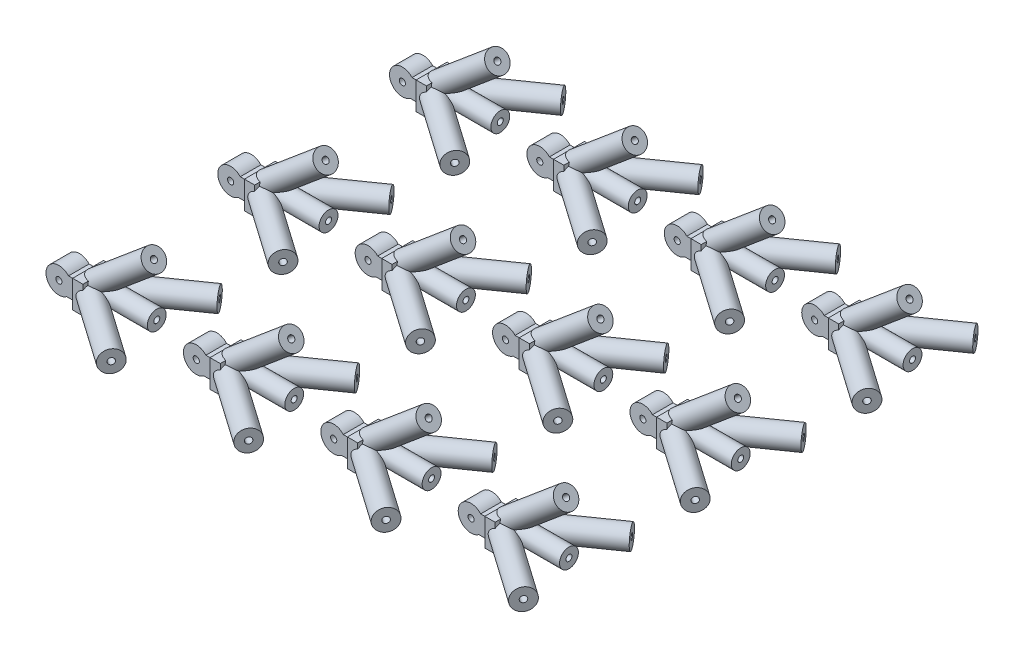
SolidWorks part; units mm, degrees
ref_plane "前视基准面" through (0, 0, 0) normal (0, 0, 1) x (1, 0, 0)
ref_plane "上视基准面" through (0, 0, 0) normal (0, 1, 0) x (1, 0, 0)
ref_plane "右视基准面" through (0, 0, 0) normal (1, 0, 0) x (0, 0, -1)
sketch "草图1" plane through (0, 0, 0) normal (0, 1, 0) x (1, 0, 0)
  line L0 (0, 0) -> (9.0107, 6.3093)
  line L1 (9.0107, 6.3093) -> (9.0107, -6.3093) construction
  line L2 (9.0107, -6.3093) -> (0, 0)
  line L3 (0, 0) -> (9.0107, 0) construction
  dimension "D1" = 11
  dimension "D2" = 35
sketch "草图2" plane through (0, 0, 0) normal (1, 0, 0) x (0, 0, -1)
  line L1 (-1.8, -1.6) -> (1.8, -1.6)
  line L2 (-1.8, -1.6) -> (-1.8, 1.6)
  line L3 (-1.8, 1.6) -> (1.8, 1.6)
  line L4 (1.8, -1.6) -> (1.8, 1.6)
  line L5 (-1.8, -1.6) -> (1.8, 1.6) construction
  line L6 (-1.8, 1.6) -> (1.8, -1.6) construction
  line L7 (-0.9562, -0.85) -> (0.9562, -0.85)
  line L8 (-0.9562, -0.85) -> (-0.9562, 0.85)
  line L9 (-0.9562, 0.85) -> (0.9562, 0.85)
  line L10 (0.9562, -0.85) -> (0.9562, 0.85)
  line L11 (-0.9562, -0.85) -> (0.9562, 0.85) construction
  line L12 (-0.9562, 0.85) -> (0.9562, -0.85) construction
  point P0 (0, 0)
  point P6 (0, 0)
  dimension "D1" = 3.2
  dimension "D2" = 1.7
  dimension "D3" = 3.6
extrude "凸台-拉伸1" add sketch "草图2" against normal blind 7
ref_plane "基准面1" through (9.0107, 0, 6.3093) normal (-0.8192, 0, -0.5736) x (-0.5736, 0, 0.8192)
sketch "草图3" plane through (9.0107, 0, 6.3093) normal (-0.8192, 0, -0.5736) x (-0.5736, 0, 0.8192)
  circle A0 centre (0, 0) radius 1.25
  circle A1 centre (0, 0) radius 0.36
  dimension "D1" = 2.5
  dimension "D2" = 0.72
extrude "凸台-拉伸2" add sketch "草图3" along normal up to surface (10.1247 mm away)
ref_plane "基准面2" through (9.0107, 0, -6.3093) normal (0.8192, 0, -0.5736) x (-0.5736, 0, -0.8192)
sketch "草图4" plane through (9.0107, 0, -6.3093) normal (0.8192, 0, -0.5736) x (-0.5736, 0, -0.8192)
  circle A0 centre (0, 0) radius 1.25
  circle A1 centre (0, 0) radius 0.35
  dimension "D1" = 0.7
  dimension "D2" = 2.5
extrude "凸台-拉伸3" add sketch "草图4" against normal up to surface (10.1247 mm away)
sketch "草图5" plane through (0, 0, 0) normal (1, 0, 0) x (0, 0, -1)
  line L4 (1.8, -1.6) -> (1.8, 1.6)
  line L5 (1.8, 1.6) -> (-1.8, 1.6)
  line L6 (-1.8, 1.6) -> (-1.8, -1.6)
  line L7 (-1.8, -1.6) -> (1.8, -1.6)
  line L8 (1.8, -1.6) -> (1.8, 1.6)
  line L9 (1.8, 1.6) -> (-1.8, 1.6)
  line L10 (-1.8, 1.6) -> (-1.8, -1.6)
  line L11 (-1.8, -1.6) -> (1.8, -1.6)
  dimension "D1" = 0
extrude "凸台-拉伸4" add sketch "草图5" along normal blind 1.2
sketch "草图6" plane through (-7, 0, 0) normal (-1, 0, 0) x (0, 0, 1)
  line L4 (-1.8, 1.6) -> (-1.8, -1.6)
  line L5 (-1.8, -1.6) -> (1.8, -1.6)
  line L6 (1.8, -1.6) -> (1.8, 1.6)
  line L7 (1.8, 1.6) -> (-1.8, 1.6)
  line L8 (-1.8, 1.6) -> (-1.8, -1.6)
  line L9 (-1.8, -1.6) -> (1.8, -1.6)
  line L10 (1.8, -1.6) -> (1.8, 1.6)
  line L11 (1.8, 1.6) -> (-1.8, 1.6)
  dimension "D1" = 0
extrude "切除-拉伸1" cut sketch "草图6" against normal up to surface (7 mm away)
sketch "草图7" plane through (0, 0, 0) normal (0, 0, 1) x (1, 0, 0)
  line L0 (-2.2, 0) -> (0, 0) construction
  line L1 (0, 1.6) -> (0, -1.6) construction
  line L2 (0, 1) -> (-1.082, 1)
  line L3 (0, 1) -> (0, -1.2)
  line L4 (0, -1.2) -> (-1.3, -1.2)
  arc A0 (-1.082, 1) -> (-1.3, -1.2) centre (-2.2, 0) ccw
  circle A1 centre (-2.2, 0) radius 0.36
  dimension "D1" = 0.72
  dimension "D2" = 1.5
  dimension "D3" = 2.2
  dimension "D4" = 2.2
  dimension "D5" = 1
extrude "凸台-拉伸5" add sketch "草图7" along normal mid plane 2.4
sketch "草图8" plane through (0, 0, 0) normal (0, 0, 1) x (1, 0, 0)
  line L0 (0, 0) -> (8, 0) construction
  line L1 (0, 0) -> (7.6604, 6.4279) construction
  line L2 (0, 1.5) -> (8, 1.5)
  dimension "D1" = 40
  dimension "D2" = 10
  dimension "D3" = 8
  dimension "D4" = 1.5
ref_plane "基准面3" through (7.6604, 6.4279, 0) normal (0.766, 0.6428, 0) x (0, 0, -1)
sketch "草图9" plane through (7.6604, 6.4279, 0) normal (0.766, 0.6428, 0) x (0, 0, -1)
  circle A0 centre (0, 0) radius 1.25
  circle A1 centre (0, 0) radius 0.35
  dimension "D1" = 0.7
  dimension "D2" = 2.5
extrude "凸台-拉伸6" add sketch "草图9" against normal up to surface (8.9511 mm away)
ref_plane "基准面4" through (8, 1.5, 0) normal (1, 0, 0) x (0, 0, -1)
sketch "草图10" plane through (8, 1.5, 0) normal (1, 0, 0) x (0, 0, -1)
  line L0 (0, -1.5) -> (0, 4.9279) construction
  line L1 (0, -1.5) -> (0, -1) construction
  circle A0 centre (0, -1) radius 1.1
  circle A1 centre (0, -1) radius 0.35
  dimension "D1" = 0.7
  dimension "D2" = 2.2
  dimension "D3" = 0.5
extrude "凸台-拉伸7" add sketch "草图10" against normal up to surface (6.4805 mm away)
pattern_linear "阵列(线性)1" count 4 spacing 16 along (-1, 0, 0) count 3 spacing 20 along (0, 0, 1) of bodies 113
